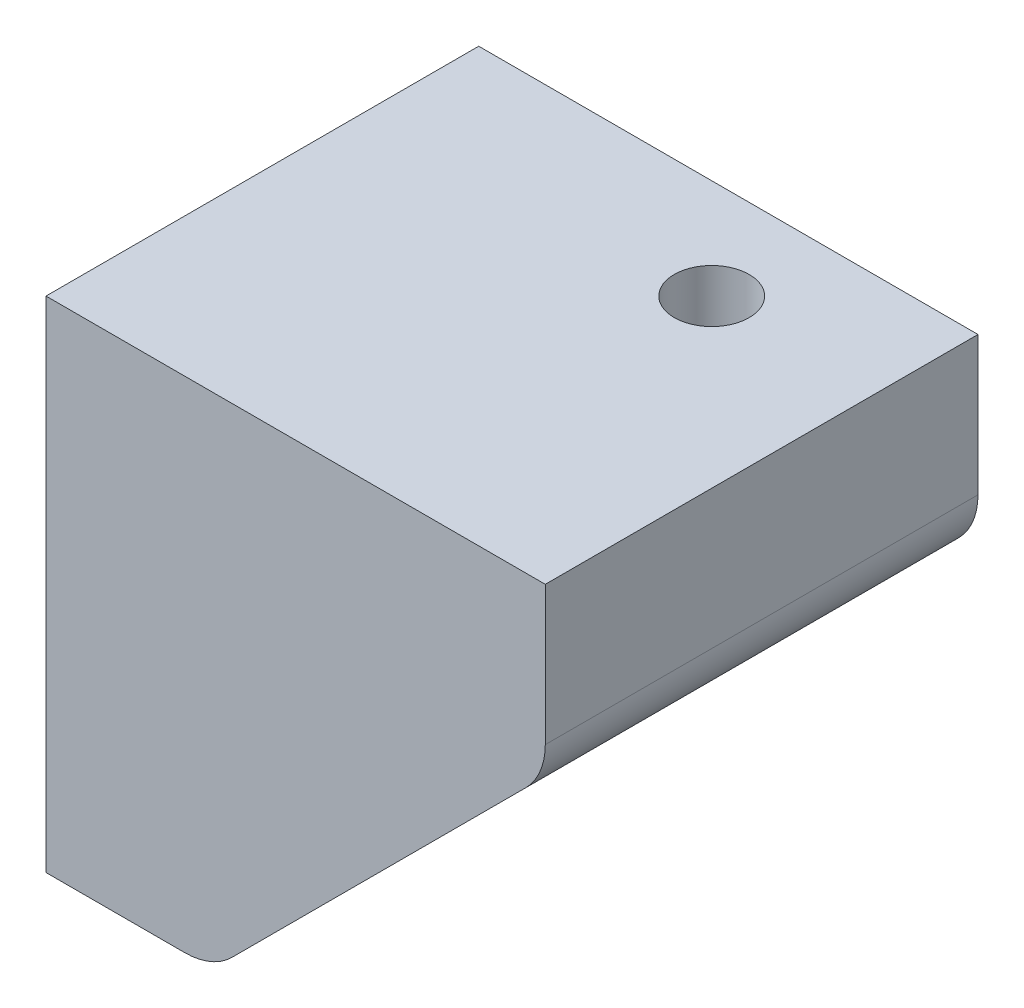
SolidWorks part; units mm, degrees
ref_plane "Front Plane" through (0, 0, 0) normal (0, 0, 1) x (1, 0, 0)
ref_plane "Top Plane" through (0, 0, 0) normal (0, 1, 0) x (1, 0, 0)
ref_plane "Right Plane" through (0, 0, 0) normal (1, 0, 0) x (0, 0, -1)
sketch "Sketch1" plane through (0, 0, 0) normal (0, 0, 1) x (1, 0, 0)
  line L0 (0, 0) -> (10, 0)
  line L1 (10, 0) -> (30, 20)
  line L2 (30, 20) -> (30, 30)
  line L3 (30, 30) -> (0, 30)
  line L4 (0, 30) -> (0, 0)
  line L5 (10, 0) -> (10, 30) construction
  line L6 (30, 20) -> (0, 20) construction
  dimension "D1" = 45
  dimension "D2" = 10
  dimension "D3" = 10
  dimension "D4" = 30
extrude "Boss-Extrude1" add sketch "Sketch1" along normal blind 26
sketch "Sketch2" plane through (0, 0, 0) normal (-1, 0, 0) x (0, 0, 1)
  line L0 (26, 20) -> (0, 20) construction
  line L1 (26, 20) -> (0, 20) construction
  line L2 (10, 20) -> (10, 0) construction
  line L3 (26, 0) -> (0, 0) construction
  line L4 (26, 30) -> (26, 0) construction
  line L5 (10, 20) -> (26, 0) construction
  circle A0 centre (18, 10) radius 2.5
  point P11 (22.7915, 10)
  point P12 (28, 0)
  dimension "D2" = 5
  dimension "D1" = 16
sketch "Sketch3" plane through (0, 30, 0) normal (0, 1, 0) x (1, 0, 0)
  line L0 (10, -26) -> (10, 0) construction
  line L1 (10, -26) -> (10, 0) construction
  line L2 (10, -12) -> (30, -12) construction
  line L3 (30, -26) -> (30, 0) construction
  line L4 (30, 0) -> (0, 0) construction
  line L5 (10, -12) -> (30, 0) construction
  circle A0 centre (20, -6) radius 2.25
  dimension "D2" = 4.5
  dimension "D1" = 12
extrude "Cut-Extrude1" cut sketch "Sketch3" against normal through all contours A0
extrude "Cut-Extrude2" cut sketch "Sketch2" against normal through all contours A0
ref_plane "Plane1" through (10, 0, 0) normal (-1, 0, 0) x (0, 0, 1)
sketch "Sketch4" plane through (10, 0, 0) normal (-1, 0, 0) x (0, 0, 1)
  circle A0 centre (18, 10) radius 2.5 construction
  circle A1 centre (18, 10) radius 2.5 construction
  circle A2 centre (18, 10) radius 5
  dimension "D1" = 10
extrude "Cut-Extrude3" cut sketch "Sketch4" against normal through all contours A2
ref_plane "Plane2" through (0, 20, 0) normal (0, 1, 0) x (1, 0, 0)
sketch "Sketch5" plane through (0, 20, 0) normal (0, 1, 0) x (1, 0, 0)
  circle A0 centre (20, -6) radius 2.25 construction
  circle A1 centre (20, -6) radius 2.25 construction
  circle A2 centre (20, -6) radius 4
  dimension "D1" = 8
extrude "Cut-Extrude4" cut sketch "Sketch5" against normal through all
chamfer "Chamfer1" distance 3 angle 45 1 edges at (10, 5, 18)
fillet "Fillet2" radius 4 2 edges at (10, 0, 13) (30, 20, 13)
